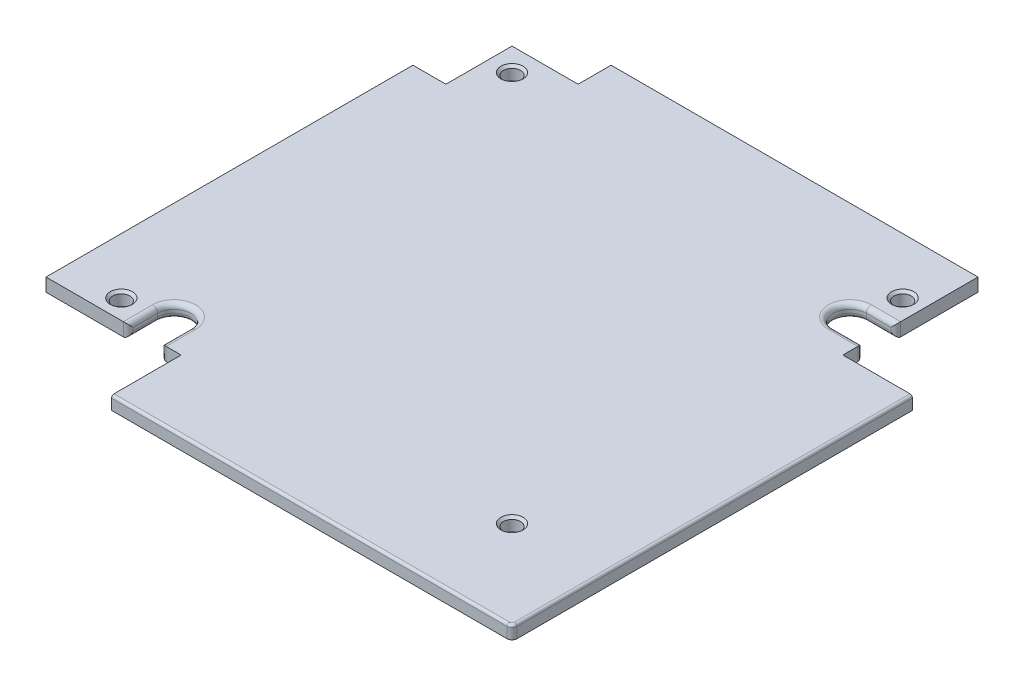
SolidWorks part; units mm, degrees
ref_plane "Front Plane" through (0, 0, 0) normal (0, 0, 1) x (1, 0, 0)
ref_plane "Top Plane" through (0, 0, 0) normal (0, 1, 0) x (1, 0, 0)
ref_plane "Right Plane" through (0, 0, 0) normal (1, 0, 0) x (0, 0, -1)
sketch "Sketch1" plane through (0, 0, 0) normal (0, 1, 0) x (1, 0, 0)
  line L0 (0, -76.2) -> (0, 76.2) construction
  line L1 (-66.25, -66.25) -> (66.25, -66.25) construction
  line L2 (-66.25, -66.25) -> (-66.25, 66.25) construction
  line L3 (-66.25, 66.25) -> (66.25, 66.25) construction
  line L4 (66.25, -66.25) -> (66.25, 66.25) construction
  line L5 (-66.25, -66.25) -> (66.25, 66.25) construction
  line L6 (-66.25, 66.25) -> (66.25, -66.25) construction
  line L11 (-66.2, 46.15) -> (-76.2, 46.15)
  line L12 (-46.15, 66.2) -> (-46.15, 76.2)
  line L15 (-46.15, 76.2) -> (65.15, 76.2)
  line L16 (86.25, 35.22) -> (86.25, -84.75)
  line L17 (84.75, -86.25) -> (-35.22, -86.25)
  line L18 (-76.2, -65.15) -> (-76.2, 46.15)
  line L19 (-66.2, 46.15) -> (-66.2, 66.2)
  line L20 (-66.2, 66.2) -> (-46.15, 66.2)
  line L21 (65.15, 76.2) -> (65.15, 51.25)
  line L22 (65.15, 35.22) -> (86.25, 35.22)
  line L23 (-76.2, -65.15) -> (-51.25, -65.15)
  line L24 (-35.22, -65.15) -> (-35.22, -86.25)
  line L25 (-51.25, -56.25) -> (-51.25, -65.15)
  line L26 (-41.25, -56.25) -> (-41.25, -65.15)
  line L27 (-41.25, -65.15) -> (-35.22, -65.15)
  line L28 (56.25, 51.25) -> (65.15, 51.25)
  line L29 (56.25, 41.25) -> (65.15, 41.25)
  line L30 (65.15, 41.25) -> (65.15, 35.22)
  circle A0 centre (-59.25, 59.25) radius 1.85
  circle A1 centre (-59.25, -59.25) radius 1.85
  circle A3 centre (59.25, -59.25) radius 1.85
  circle A4 centre (59.25, 59.25) radius 1.85
  circle A5 centre (-59.25, 59.25) radius 2.6
  circle A6 centre (59.25, 59.25) radius 2.6
  circle A7 centre (59.25, -59.25) radius 2.6
  circle A8 centre (-59.25, -59.25) radius 2.6
  arc A9 (86.25, -84.75) -> (84.75, -86.25) centre (84.75, -84.75) cw
  arc A11 (-41.25, -56.25) -> (-51.25, -56.25) centre (-46.25, -56.25) ccw
  arc A12 (56.25, 41.25) -> (56.25, 51.25) centre (56.25, 46.25) cw
  point P0 (0, 0)
  point P16 (0, 0)
  dimension "D2" = 3.7
  dimension "D3" = 7
  dimension "D7" = 20
  dimension "D9" = 5.2
  dimension "D10" = 1.5
  dimension "D14" = 20
  dimension "D16" = 10
  dimension "D1" = 132.5
  dimension "D4" = 9.95
  dimension "D5" = 20
  dimension "D6" = 20.1
  dimension "D8" = 9.95
  dimension "D11" = 10
  dimension "D12" = 40.98
  dimension "D13" = 21.1
  dimension "D15" = 10
  dimension "D17" = 40.98
extrude "Boss-Extrude1" add sketch "Sketch1" along normal mid plane 4 contours L18 L17 L16 L15 L12 L11 A8 A7 A6 A5 | A5 A0 | A6 A4 | A7 A3 | A8 A1 region at (6.1445, 0, 6.1445) region at (-61.7765, 0, -59.25) region at (56.7235, 0, -59.25) region at (56.7235, 0, 59.25) region at (-61.7765, 0, 59.25)
chamfer "Chamfer2" distance 1.5 angle 45 4 edges at (-59.25, 2, -57.4) (59.25, 2, -57.4) (-59.25, 2, 61.1) (59.25, 2, 61.1)
extrude "Cut-Extrude2" cut sketch "Sketch1<4>" along normal up to surface (2 mm away) from surface contours A5 A0 | A8 A1 | A7 A3 | A6 A4 region at (-61.7765, 0, -59.25) region at (56.7235, 0, -59.25) region at (56.7235, 0, 59.25) region at (-61.7765, 0, 59.25) up to face at (59.25, 2, -55.9) starting at face at (-0.3276, -2, -0.3276)
sketch "Sketch1<4>" plane through (0, 0, 0) normal (0, 1, 0) x (1, 0, 0) same geometry as "Sketch1"
fillet "Fillet1" radius 0.75 3 edges at (86.25, 2, 24.765) (85.8107, 2, 85.8107) (24.765, 2, 86.25)
fillet "Fillet2" radius 1.5 16 edges at (60.7, -2, -41.25) (51.25, -2, -46.25) (60.7, 2, -41.25) (51.25, 2, -46.25) (-51.25, -2, 60.7) (-46.25, -2, 51.25) (-41.25, 2, 60.7) (-51.25, 2, 60.7) (60.7, -2, -51.25) (60.7, 2, -51.25) (-41.25, -2, 60.7) (-46.25, 2, 51.25) (65.15, 0, -51.25) (65.15, 0, -41.25) (-41.25, 0, 65.15) (-51.25, 0, 65.15)
